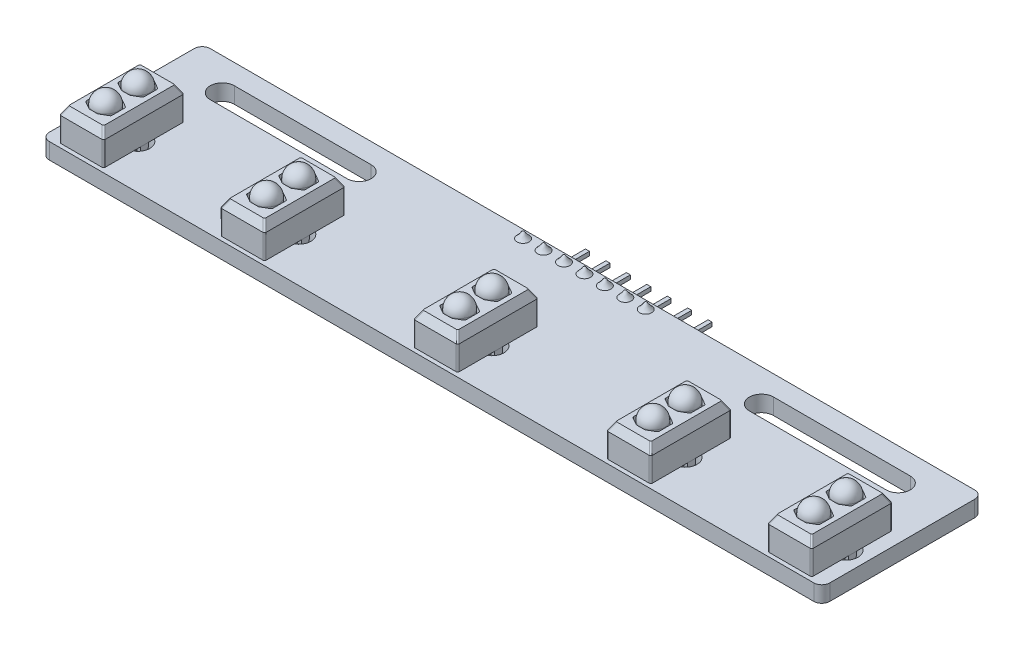
SolidWorks part; units mm, degrees
ref_plane "Front Plane" through (0, 0, 0) normal (0, 0, 1) x (1, 0, 0)
ref_plane "Top Plane" through (0, 0, 0) normal (0, 1, 0) x (1, 0, 0)
ref_plane "Right Plane" through (0, 0, 0) normal (1, 0, 0) x (0, 0, -1)
sketch "Sketch1" plane through (0, 0, 0) normal (0, 1, 0) x (1, 0, 0)
  line L0 (-42, 6) -> (-25, 6) construction
  line L1 (47.5, -10) -> (-47.5, -10)
  line L2 (48.5, -9) -> (48.5, 9)
  line L3 (47.5, 10) -> (-47.5, 10)
  line L4 (-48.5, -9) -> (-48.5, 9)
  line L5 (48.5, -10) -> (-48.5, 10) construction
  line L6 (48.5, 10) -> (-48.5, -10) construction
  line L7 (-42, 7.5) -> (-25, 7.5)
  line L8 (-42, 4.5) -> (-25, 4.5)
  line L9 (0, -55) -> (0, 55) construction
  line L10 (42, 6) -> (25, 6) construction
  line L11 (42, 7.5) -> (25, 7.5)
  line L12 (42, 4.5) -> (25, 4.5)
  arc A0 (-42, 7.5) -> (-42, 4.5) centre (-42, 6) ccw
  arc A1 (-25, 4.5) -> (-25, 7.5) centre (-25, 6) ccw
  arc A2 (42, 7.5) -> (42, 4.5) centre (42, 6) cw
  arc A3 (25, 4.5) -> (25, 7.5) centre (25, 6) cw
  circle A4 centre (-46, -4.5) radius 1.5
  circle A5 centre (-42, -4.5) radius 1.5
  circle A6 centre (-22, -4.5) radius 1.5
  circle A7 centre (-26, -4.5) radius 1.5
  circle A8 centre (-2, -4.5) radius 1.5
  circle A9 centre (2, -4.5) radius 1.5
  circle A10 centre (22, -4.5) radius 1.5
  circle A11 centre (42, -4.5) radius 1.5
  circle A12 centre (26, -4.5) radius 1.5
  circle A13 centre (46, -4.5) radius 1.5
  arc A14 (47.5, -10) -> (48.5, -9) centre (47.5, -9) ccw
  arc A15 (48.5, 9) -> (47.5, 10) centre (47.5, 9) ccw
  arc A16 (-47.5, -10) -> (-48.5, -9) centre (-47.5, -9) cw
  arc A17 (-47.5, 10) -> (-48.5, 9) centre (-47.5, 9) ccw
  point P0 (0, 0)
  point P8 (-33.5, 6)
  point P13 (-43.5, 6)
  point P14 (-23.5, 6)
  point P19 (33.5, 6)
  dimension "D7" = 3
  dimension "D13" = 1
  dimension "D1" = 97
  dimension "D2" = 20
  dimension "D3" = 20
  dimension "D4" = 3
  dimension "D5" = 2.5
  dimension "D6" = 5
  dimension "D8" = 4
  dimension "D9" = 5.5
  dimension "D10" = 2.5
  dimension "D12" = 2
  dimension "D11" = 2
extrude "Boss-Extrude1" add sketch "Sketch1" along normal blind 2
sketch "Sketch2" plane through (0, 2, 0) normal (0, 1, 0) x (1, 0, 0)
  line L0 (-47.5, -4.5) -> (-40.5, -4.5) construction
  line L1 (-46.75, -9.5) -> (-41.25, -9.5)
  line L2 (-46.75, -9.5) -> (-46.75, 0.5)
  line L3 (-46.75, 0.5) -> (-41.25, 0.5)
  line L4 (-41.25, -9.5) -> (-41.25, 0.5)
  line L5 (-46.75, -9.5) -> (-41.25, 0.5) construction
  line L6 (-46.75, 0.5) -> (-41.25, -9.5) construction
  line L7 (-26.75, -9.5) -> (-26.75, 0.5)
  line L8 (-26.75, -9.5) -> (-21.25, -9.5)
  line L9 (-21.25, -9.5) -> (-21.25, 0.5)
  line L10 (-26.75, 0.5) -> (-21.25, 0.5)
  line L11 (-2.75, -9.5) -> (-2.75, 0.5)
  line L12 (-2.75, 0.5) -> (2.75, 0.5)
  line L13 (2.75, -9.5) -> (2.75, 0.5)
  line L14 (-2.75, -9.5) -> (2.75, -9.5)
  line L15 (0, -1.1) -> (0, 1.1) construction
  line L16 (46.75, 0.5) -> (41.25, 0.5)
  line L17 (41.25, -9.5) -> (41.25, 0.5)
  line L18 (46.75, -9.5) -> (41.25, -9.5)
  line L19 (46.75, -9.5) -> (46.75, 0.5)
  line L20 (26.75, -9.5) -> (21.25, -9.5)
  line L21 (21.25, -9.5) -> (21.25, 0.5)
  line L22 (26.75, 0.5) -> (21.25, 0.5)
  line L23 (26.75, -9.5) -> (26.75, 0.5)
  circle A0 centre (-42, -4.5) radius 1.5 construction
  circle A1 centre (-46, -4.5) radius 1.5 construction
  point P0 (-44, -4.5)
  dimension "D1" = 10
  dimension "D2" = 5.5
  dimension "D3" = 2
  dimension "D4" = 2
  dimension "D5" = 2
extrude "Boss-Extrude2" add sketch "Sketch2" along normal blind 4
chamfer "Chamfer2" distance 1 angle 30 20 edges at (44, 6, 9.5) (41.25, 6, 4.5) (44, 6, -0.5) (46.75, 6, 4.5) (24, 6, 9.5) (21.25, 6, 4.5) (24, 6, -0.5) (26.75, 6, 4.5) (0, 6, 9.5) (-2.75, 6, 4.5) (0, 6, -0.5) (2.75, 6, 4.5) (-21.25, 6, 4.5) (-24, 6, 9.5) (-26.75, 6, 4.5) (-24, 6, -0.5) (-44, 6, 9.5) (-46.75, 6, 4.5) (-44, 6, -0.5) (-41.25, 6, 4.5) first distance on face at (44, 4, 9.5) first distance on face at (41.25, 3.3333, 4.5) first distance on face at (44, 4, -0.5) first distance on face at (46.75, 3.3333, 4.5) first distance on face at (24, 4, 9.5) first distance on face at (21.25, 3.3333, 4.5) first distance on face at (24, 4, -0.5) first distance on face at (26.75, 3.3333, 4.5) first distance on face at (0, 4, 9.5) first distance on face at (-2.75, 3.3333, 4.5) first distance on face at (0, 4, -0.5) first distance on face at (2.75, 3.3333, 4.5) first distance on face at (-21.25, 3.3333, 4.5) first distance on face at (-24, 4, 9.5) first distance on face at (-26.75, 3.3333, 4.5) first distance on face at (-24, 4, -0.5) first distance on face at (-44, 4, 9.5) first distance on face at (-46.75, 3.3333, 4.5) first distance on face at (-44, 4, -0.5) first distance on face at (-41.25, 3.3333, 4.5)
fillet "Fillet1" radius 0.2 40 edges at (41.25, 3.5, -0.5) (41.5387, 5.5, -0.2113) (46.75, 3.5, -0.5) (46.4613, 5.5, -0.2113) (41.25, 3.5, 9.5) (41.5387, 5.5, 9.2113) (46.75, 3.5, 9.5) (46.4613, 5.5, 9.2113) (26.75, 3.5, 9.5) (26.4613, 5.5, 9.2113) (21.25, 3.5, 9.5) (21.5387, 5.5, 9.2113) (21.25, 3.5, -0.5) (21.5387, 5.5, -0.2113) (26.4613, 5.5, -0.2113) (26.75, 3.5, -0.5) (2.75, 3.5, -0.5) (-2.75, 3.5, -0.5) (2.75, 3.5, 9.5) (-2.75, 3.5, 9.5) (-2.4613, 5.5, 9.2113) (2.4613, 5.5, 9.2113) (2.4613, 5.5, -0.2113) (-2.4613, 5.5, -0.2113) (-21.5387, 5.5, -0.2113) (-26.4613, 5.5, -0.2113) (-21.5387, 5.5, 9.2113) (-26.4613, 5.5, 9.2113) (-26.75, 3.5, 9.5) (-21.25, 3.5, 9.5) (-26.75, 3.5, -0.5) (-21.25, 3.5, -0.5) (-41.25, 3.5, -0.5) (-41.5387, 5.5, -0.2113) (-46.4613, 5.5, -0.2113) (-46.75, 3.5, -0.5) (-41.5387, 5.5, 9.2113) (-41.25, 3.5, 9.5) (-46.4613, 5.5, 9.2113) (-46.75, 3.5, 9.5)
sketch "Sketch3" plane through (0, 6, 0) normal (0, 1, 0) x (1, 0, 0)
  line L0 (-46.1726, -0.2506) -> (-46.1726, -8.7494) construction
  line L1 (-44.4849, -0.9777) -> (-43.5204, -0.9777)
  line L2 (-45.5889, -1.6996) -> (-45.5889, -3.3004)
  line L3 (-45.4889, -3.4736) -> (-44.5849, -3.9955)
  line L4 (-43.4204, -3.9955) -> (-42.5164, -3.4736)
  line L5 (-42.4164, -3.3004) -> (-42.4164, -1.6996)
  line L6 (-42.5164, -1.5264) -> (-43.4204, -1.0045)
  line L7 (-44.5849, -1.0045) -> (-45.4889, -1.5264)
  line L8 (-44.0026, -2.5) -> (-42.7184, -2.5) construction
  line L9 (-44.4849, -4.0223) -> (-43.5204, -4.0223)
  line L10 (-46.1726, -4.5) -> (-42.0545, -4.5) construction
  line L11 (-44.5849, -7.9955) -> (-45.4889, -7.4736)
  line L12 (-44.4849, -8.0223) -> (-43.5204, -8.0223)
  line L13 (-42.5164, -7.4736) -> (-43.4204, -7.9955)
  line L14 (-42.4164, -5.6996) -> (-42.4164, -7.3004)
  line L15 (-43.4204, -5.0045) -> (-42.5164, -5.5264)
  line L16 (-44.4849, -4.9777) -> (-43.5204, -4.9777)
  line L17 (-45.4889, -5.5264) -> (-44.5849, -5.0045)
  line L18 (-45.5889, -7.3004) -> (-45.5889, -5.6996)
  line L19 (-25.5889, -1.6996) -> (-25.5889, -3.3004)
  line L20 (-25.4889, -3.4736) -> (-24.5849, -3.9955)
  line L21 (-24.4849, -4.0223) -> (-23.5204, -4.0223)
  line L22 (-23.4204, -3.9955) -> (-22.5164, -3.4736)
  line L23 (-22.4164, -3.3004) -> (-22.4164, -1.6996)
  line L24 (-22.5164, -1.5264) -> (-23.4204, -1.0045)
  line L25 (-24.4849, -0.9777) -> (-23.5204, -0.9777)
  line L26 (-24.5849, -1.0045) -> (-25.4889, -1.5264)
  line L27 (-24.5849, -7.9955) -> (-25.4889, -7.4736)
  line L28 (-25.5889, -7.3004) -> (-25.5889, -5.6996)
  line L29 (-25.4889, -5.5264) -> (-24.5849, -5.0045)
  line L30 (-24.4849, -4.9777) -> (-23.5204, -4.9777)
  line L31 (-23.4204, -5.0045) -> (-22.5164, -5.5264)
  line L32 (-22.4164, -5.6996) -> (-22.4164, -7.3004)
  line L33 (-22.5164, -7.4736) -> (-23.4204, -7.9955)
  line L34 (-24.4849, -8.0223) -> (-23.5204, -8.0223)
  line L35 (-1.5889, -1.6996) -> (-1.5889, -3.3004)
  line L36 (-1.4889, -3.4736) -> (-0.5849, -3.9955)
  line L37 (-0.4849, -4.0223) -> (0.4796, -4.0223)
  line L38 (0.5796, -3.9955) -> (1.4836, -3.4736)
  line L39 (1.5836, -3.3004) -> (1.5836, -1.6996)
  line L40 (1.4836, -1.5264) -> (0.5796, -1.0045)
  line L41 (-0.4849, -0.9777) -> (0.4796, -0.9777)
  line L42 (-0.5849, -1.0045) -> (-1.4889, -1.5264)
  line L43 (-0.5849, -7.9955) -> (-1.4889, -7.4736)
  line L44 (-1.5889, -7.3004) -> (-1.5889, -5.6996)
  line L45 (-1.4889, -5.5264) -> (-0.5849, -5.0045)
  line L46 (-0.4849, -4.9777) -> (0.4796, -4.9777)
  line L47 (0.5796, -5.0045) -> (1.4836, -5.5264)
  line L48 (1.5836, -5.6996) -> (1.5836, -7.3004)
  line L49 (1.4836, -7.4736) -> (0.5796, -7.9955)
  line L50 (-0.4849, -8.0223) -> (0.4796, -8.0223)
  line L51 (0, -3.3) -> (0, 3.3) construction
  line L52 (24.4849, -8.0223) -> (23.5204, -8.0223)
  line L53 (22.5164, -7.4736) -> (23.4204, -7.9955)
  line L54 (22.4164, -5.6996) -> (22.4164, -7.3004)
  line L55 (23.4204, -5.0045) -> (22.5164, -5.5264)
  line L56 (24.4849, -4.9777) -> (23.5204, -4.9777)
  line L57 (25.4889, -5.5264) -> (24.5849, -5.0045)
  line L58 (25.5889, -7.3004) -> (25.5889, -5.6996)
  line L59 (24.5849, -7.9955) -> (25.4889, -7.4736)
  line L60 (24.5849, -1.0045) -> (25.4889, -1.5264)
  line L61 (24.4849, -0.9777) -> (23.5204, -0.9777)
  line L62 (22.5164, -1.5264) -> (23.4204, -1.0045)
  line L63 (22.4164, -3.3004) -> (22.4164, -1.6996)
  line L64 (23.4204, -3.9955) -> (22.5164, -3.4736)
  line L65 (24.4849, -4.0223) -> (23.5204, -4.0223)
  line L66 (25.4889, -3.4736) -> (24.5849, -3.9955)
  line L67 (25.5889, -1.6996) -> (25.5889, -3.3004)
  line L68 (44.4849, -8.0223) -> (43.5204, -8.0223)
  line L69 (42.5164, -7.4736) -> (43.4204, -7.9955)
  line L70 (42.4164, -5.6996) -> (42.4164, -7.3004)
  line L71 (43.4204, -5.0045) -> (42.5164, -5.5264)
  line L72 (44.4849, -4.9777) -> (43.5204, -4.9777)
  line L73 (45.4889, -5.5264) -> (44.5849, -5.0045)
  line L74 (45.5889, -7.3004) -> (45.5889, -5.6996)
  line L75 (44.5849, -7.9955) -> (45.4889, -7.4736)
  line L76 (44.5849, -1.0045) -> (45.4889, -1.5264)
  line L77 (44.4849, -0.9777) -> (43.5204, -0.9777)
  line L78 (42.5164, -1.5264) -> (43.4204, -1.0045)
  line L79 (42.4164, -3.3004) -> (42.4164, -1.6996)
  line L80 (43.4204, -3.9955) -> (42.5164, -3.4736)
  line L81 (44.4849, -4.0223) -> (43.5204, -4.0223)
  line L82 (45.4889, -3.4736) -> (44.5849, -3.9955)
  line L83 (45.5889, -1.6996) -> (45.5889, -3.3004)
  circle A0 centre (-44.0026, -2.5) radius 1.5
  circle A1 centre (-44.0026, -2.5) radius 1.5863 construction
  arc A2 (-44.4849, -4.0223) -> (-44.5849, -3.9955) centre (-44.4849, -3.8223) cw
  arc A3 (-43.5204, -4.0223) -> (-43.4204, -3.9955) centre (-43.5204, -3.8223) ccw
  arc A4 (-43.5204, -0.9777) -> (-43.4204, -1.0045) centre (-43.5204, -1.1777) cw
  arc A5 (-44.4849, -0.9777) -> (-44.5849, -1.0045) centre (-44.4849, -1.1777) ccw
  arc A6 (-42.4164, -1.6996) -> (-42.5164, -1.5264) centre (-42.6164, -1.6996) ccw
  arc A7 (-42.5164, -3.4736) -> (-42.4164, -3.3004) centre (-42.6164, -3.3004) ccw
  arc A8 (-45.5889, -3.3004) -> (-45.4889, -3.4736) centre (-45.3889, -3.3004) ccw
  arc A9 (-45.5889, -1.6996) -> (-45.4889, -1.5264) centre (-45.3889, -1.6996) cw
  arc A10 (-44.4849, -8.0223) -> (-44.5849, -7.9955) centre (-44.4849, -7.8223) cw
  arc A11 (-43.5204, -8.0223) -> (-43.4204, -7.9955) centre (-43.5204, -7.8223) ccw
  arc A12 (-42.4164, -7.3004) -> (-42.5164, -7.4736) centre (-42.6164, -7.3004) cw
  arc A13 (-42.5164, -5.5264) -> (-42.4164, -5.6996) centre (-42.6164, -5.6996) cw
  arc A14 (-43.5204, -4.9777) -> (-43.4204, -5.0045) centre (-43.5204, -5.1777) cw
  arc A15 (-44.4849, -4.9777) -> (-44.5849, -5.0045) centre (-44.4849, -5.1777) ccw
  arc A16 (-45.5889, -5.6996) -> (-45.4889, -5.5264) centre (-45.3889, -5.6996) cw
  arc A17 (-45.5889, -7.3004) -> (-45.4889, -7.4736) centre (-45.3889, -7.3004) ccw
  arc A18 (-25.5889, -1.6996) -> (-25.4889, -1.5264) centre (-25.3889, -1.6996) cw
  arc A19 (-25.5889, -3.3004) -> (-25.4889, -3.4736) centre (-25.3889, -3.3004) ccw
  arc A20 (-24.4849, -4.0223) -> (-24.5849, -3.9955) centre (-24.4849, -3.8223) cw
  arc A21 (-23.5204, -4.0223) -> (-23.4204, -3.9955) centre (-23.5204, -3.8223) ccw
  arc A22 (-22.5164, -3.4736) -> (-22.4164, -3.3004) centre (-22.6164, -3.3004) ccw
  arc A23 (-22.4164, -1.6996) -> (-22.5164, -1.5264) centre (-22.6164, -1.6996) ccw
  arc A24 (-23.5204, -0.9777) -> (-23.4204, -1.0045) centre (-23.5204, -1.1777) cw
  arc A25 (-24.4849, -0.9777) -> (-24.5849, -1.0045) centre (-24.4849, -1.1777) ccw
  arc A26 (-25.5889, -7.3004) -> (-25.4889, -7.4736) centre (-25.3889, -7.3004) ccw
  arc A27 (-25.5889, -5.6996) -> (-25.4889, -5.5264) centre (-25.3889, -5.6996) cw
  arc A28 (-24.4849, -4.9777) -> (-24.5849, -5.0045) centre (-24.4849, -5.1777) ccw
  arc A29 (-23.5204, -4.9777) -> (-23.4204, -5.0045) centre (-23.5204, -5.1777) cw
  arc A30 (-22.5164, -5.5264) -> (-22.4164, -5.6996) centre (-22.6164, -5.6996) cw
  arc A31 (-22.4164, -7.3004) -> (-22.5164, -7.4736) centre (-22.6164, -7.3004) cw
  arc A32 (-23.5204, -8.0223) -> (-23.4204, -7.9955) centre (-23.5204, -7.8223) ccw
  arc A33 (-24.4849, -8.0223) -> (-24.5849, -7.9955) centre (-24.4849, -7.8223) cw
  arc A34 (-1.5889, -3.3004) -> (-1.4889, -3.4736) centre (-1.3889, -3.3004) ccw
  arc A35 (-0.4849, -4.0223) -> (-0.5849, -3.9955) centre (-0.4849, -3.8223) cw
  arc A36 (0.4796, -4.0223) -> (0.5796, -3.9955) centre (0.4796, -3.8223) ccw
  arc A37 (1.4836, -3.4736) -> (1.5836, -3.3004) centre (1.3836, -3.3004) ccw
  arc A38 (1.5836, -1.6996) -> (1.4836, -1.5264) centre (1.3836, -1.6996) ccw
  arc A39 (0.4796, -0.9777) -> (0.5796, -1.0045) centre (0.4796, -1.1777) cw
  arc A40 (-0.4849, -0.9777) -> (-0.5849, -1.0045) centre (-0.4849, -1.1777) ccw
  arc A41 (-1.5889, -1.6996) -> (-1.4889, -1.5264) centre (-1.3889, -1.6996) cw
  arc A42 (-1.5889, -7.3004) -> (-1.4889, -7.4736) centre (-1.3889, -7.3004) ccw
  arc A43 (-1.5889, -5.6996) -> (-1.4889, -5.5264) centre (-1.3889, -5.6996) cw
  arc A44 (-0.4849, -4.9777) -> (-0.5849, -5.0045) centre (-0.4849, -5.1777) ccw
  arc A45 (0.4796, -4.9777) -> (0.5796, -5.0045) centre (0.4796, -5.1777) cw
  arc A46 (1.4836, -5.5264) -> (1.5836, -5.6996) centre (1.3836, -5.6996) cw
  arc A47 (1.5836, -7.3004) -> (1.4836, -7.4736) centre (1.3836, -7.3004) cw
  arc A48 (0.4796, -8.0223) -> (0.5796, -7.9955) centre (0.4796, -7.8223) ccw
  arc A49 (-0.4849, -8.0223) -> (-0.5849, -7.9955) centre (-0.4849, -7.8223) cw
  arc A50 (24.4849, -8.0223) -> (24.5849, -7.9955) centre (24.4849, -7.8223) ccw
  arc A51 (23.5204, -8.0223) -> (23.4204, -7.9955) centre (23.5204, -7.8223) cw
  arc A52 (22.4164, -7.3004) -> (22.5164, -7.4736) centre (22.6164, -7.3004) ccw
  arc A53 (22.5164, -5.5264) -> (22.4164, -5.6996) centre (22.6164, -5.6996) ccw
  arc A54 (23.5204, -4.9777) -> (23.4204, -5.0045) centre (23.5204, -5.1777) ccw
  arc A55 (24.4849, -4.9777) -> (24.5849, -5.0045) centre (24.4849, -5.1777) cw
  arc A56 (25.5889, -5.6996) -> (25.4889, -5.5264) centre (25.3889, -5.6996) ccw
  arc A57 (25.5889, -7.3004) -> (25.4889, -7.4736) centre (25.3889, -7.3004) cw
  arc A58 (25.5889, -1.6996) -> (25.4889, -1.5264) centre (25.3889, -1.6996) ccw
  arc A59 (24.4849, -0.9777) -> (24.5849, -1.0045) centre (24.4849, -1.1777) cw
  arc A60 (23.5204, -0.9777) -> (23.4204, -1.0045) centre (23.5204, -1.1777) ccw
  arc A61 (22.4164, -1.6996) -> (22.5164, -1.5264) centre (22.6164, -1.6996) cw
  arc A62 (22.5164, -3.4736) -> (22.4164, -3.3004) centre (22.6164, -3.3004) cw
  arc A63 (23.5204, -4.0223) -> (23.4204, -3.9955) centre (23.5204, -3.8223) cw
  arc A64 (24.4849, -4.0223) -> (24.5849, -3.9955) centre (24.4849, -3.8223) ccw
  arc A65 (25.5889, -3.3004) -> (25.4889, -3.4736) centre (25.3889, -3.3004) cw
  arc A66 (44.4849, -8.0223) -> (44.5849, -7.9955) centre (44.4849, -7.8223) ccw
  arc A67 (43.5204, -8.0223) -> (43.4204, -7.9955) centre (43.5204, -7.8223) cw
  arc A68 (42.4164, -7.3004) -> (42.5164, -7.4736) centre (42.6164, -7.3004) ccw
  arc A69 (42.5164, -5.5264) -> (42.4164, -5.6996) centre (42.6164, -5.6996) ccw
  arc A70 (43.5204, -4.9777) -> (43.4204, -5.0045) centre (43.5204, -5.1777) ccw
  arc A71 (44.4849, -4.9777) -> (44.5849, -5.0045) centre (44.4849, -5.1777) cw
  arc A72 (45.5889, -5.6996) -> (45.4889, -5.5264) centre (45.3889, -5.6996) ccw
  arc A73 (45.5889, -7.3004) -> (45.4889, -7.4736) centre (45.3889, -7.3004) cw
  arc A74 (44.4849, -0.9777) -> (44.5849, -1.0045) centre (44.4849, -1.1777) cw
  arc A75 (43.5204, -0.9777) -> (43.4204, -1.0045) centre (43.5204, -1.1777) ccw
  arc A76 (42.4164, -1.6996) -> (42.5164, -1.5264) centre (42.6164, -1.6996) cw
  arc A77 (42.5164, -3.4736) -> (42.4164, -3.3004) centre (42.6164, -3.3004) cw
  arc A78 (43.5204, -4.0223) -> (43.4204, -3.9955) centre (43.5204, -3.8223) cw
  arc A79 (44.4849, -4.0223) -> (44.5849, -3.9955) centre (44.4849, -3.8223) ccw
  arc A80 (45.5889, -3.3004) -> (45.4889, -3.4736) centre (45.3889, -3.3004) cw
  arc A81 (45.5889, -1.6996) -> (45.4889, -1.5264) centre (45.3889, -1.6996) ccw
  circle A82 centre (-44.0026, -6.5) radius 1.5
  circle A83 centre (-24.0026, -2.5) radius 1.5
  circle A84 centre (-24.0026, -6.5) radius 1.5
  circle A85 centre (-0.0026, -6.5) radius 1.5
  circle A86 centre (-0.0026, -2.5) radius 1.5
  circle A87 centre (44.0026, -6.5) radius 1.5
  circle A88 centre (44.0026, -2.5) radius 1.5
  circle A89 centre (24.0026, -6.5) radius 1.5
  circle A90 centre (24.0026, -2.5) radius 1.5
  point P2 (-46.1726, -4.5)
  point P17 (-44.5384, -4.0223)
  point P20 (-43.4668, -4.0223)
  point P23 (-43.4668, -0.9777)
  point P26 (-44.5384, -0.9777)
  dimension "D1" = 3
  dimension "D3" = 0.2
  dimension "D2" = 2
  dimension "D4" = 2
  dimension "D5" = 2
  dimension "D6" = 2
  dimension "D7" = 2
extrude "Cut-Extrude1" cut sketch "Sketch3" against normal blind 1.5
sketch "Sketch5" plane through (0, 6, 0) normal (0, 1, 0) x (1, 0, 0)
  line L0 (-43.5204, -0.9777) -> (-44.4849, -0.9777) construction
  line L1 (-44.0026, -0.9777) -> (-44.0026, -8.0223) construction
  line L2 (-44.4849, -8.0223) -> (-43.5204, -8.0223) construction
  line L3 (-42.4164, -2.5) -> (-44.0026, -2.5) construction
  line L4 (-42.4164, -3.3004) -> (-42.4164, -1.6996) construction
  line L5 (-44.0026, -1) -> (-44.0026, -4)
  line L6 (-46.75, -4.5) -> (-41.9193, -4.5) construction
  line L7 (-46.75, -9.3) -> (-46.75, 0.3) construction
  line L8 (-44.0026, -8) -> (-44.0026, -5)
  arc A0 (-44.0026, -4) -> (-44.0026, -1) centre (-44.0026, -2.5) ccw
  arc A1 (-44.0026, -5) -> (-44.0026, -8) centre (-44.0026, -6.5) cw
  dimension "D1" = 3
revolve "Revolve4" add sketch "Sketch5" angle 180 about L5
pattern_linear "LPattern2" count 2 spacing 20 along (1, 0, 0) of "Revolve4"
pattern_linear "LPattern1" count 2 spacing 44 along (1, 0, 0) of "Revolve4"
mirror "Mirror1" about plane through (0, 0, 0) normal (1, 0, 0) of "LPattern2", "Revolve4"
sketch "Sketch7" plane through (0, 0, 0) normal (0, -1, 0) x (1, 0, 0)
  line L0 (47.5, -10) -> (-47.5, -10) construction
  line L1 (-0.25, -9.25) -> (0.25, -9.25)
  line L2 (-0.25, -9.25) -> (-0.25, -8.75)
  line L3 (-0.25, -8.75) -> (0.25, -8.75)
  line L4 (0.25, -9.25) -> (0.25, -8.75)
  line L5 (-0.25, -9.25) -> (0.25, -8.75) construction
  line L6 (-0.25, -8.75) -> (0.25, -9.25) construction
  point P0 (0, -9)
  dimension "D1" = 0.5
  dimension "D2" = 0.5
  dimension "D3" = 1
sketch "Sketch8" plane through (0, 0, 0) normal (1, 0, 0) x (0, 0, -1)
  line L0 (9, 0) -> (9, -2.5)
  line L1 (9.25, 0) -> (8.75, 0) construction
  line L2 (10, -3.5) -> (17, -3.5)
  arc A0 (9, -2.5) -> (10, -3.5) centre (10, -2.5) ccw
  point P7 (9, -3.5)
  dimension "D3" = 1
  dimension "D1" = 3.5
  dimension "D2" = 8
sketch "Sketch9" plane through (0, 2, 0) normal (0, -1, 0) x (1, 0, 0)
  line L0 (-46.75, 3.201) -> (-46.75, 5.799) construction
  line L1 (-46.75, 4.9284) -> (-46.25, 4.9284)
  line L2 (-46.75, 4.9284) -> (-46.75, 3.9284)
  line L3 (-46.75, 3.9284) -> (-46.25, 3.9284)
  line L4 (-46.25, 4.9284) -> (-46.25, 3.9284)
  line L5 (-41.25, 5.799) -> (-41.25, 3.201) construction
  line L6 (-41.25, 4.9159) -> (-41.75, 4.9159)
  line L7 (-41.25, 4.9159) -> (-41.25, 3.9159)
  line L8 (-41.25, 3.9159) -> (-41.75, 3.9159)
  line L9 (-41.75, 4.9159) -> (-41.75, 3.9159)
  line L10 (-44.5, 4.5) -> (-43.5, 4.5) construction
  line L11 (-41.75, 4.4159) -> (-41.25, 4.4159) construction
  line L12 (-26.75, 4.9284) -> (-26.75, 3.9284)
  line L13 (-26.75, 4.9284) -> (-26.25, 4.9284)
  line L14 (-26.25, 4.9284) -> (-26.25, 3.9284)
  line L15 (-26.75, 3.9284) -> (-26.25, 3.9284)
  line L16 (-21.25, 4.9159) -> (-21.25, 3.9159)
  line L17 (-21.25, 4.9159) -> (-21.75, 4.9159)
  line L18 (-21.75, 4.9159) -> (-21.75, 3.9159)
  line L19 (-21.25, 3.9159) -> (-21.75, 3.9159)
  line L20 (-2.75, 4.9284) -> (-2.75, 3.9284)
  line L21 (-2.75, 3.9284) -> (-2.25, 3.9284)
  line L22 (-2.25, 4.9284) -> (-2.25, 3.9284)
  line L23 (-2.75, 4.9284) -> (-2.25, 4.9284)
  line L24 (2.75, 4.9159) -> (2.75, 3.9159)
  line L25 (2.75, 3.9159) -> (2.25, 3.9159)
  line L26 (2.25, 4.9159) -> (2.25, 3.9159)
  line L27 (2.75, 4.9159) -> (2.25, 4.9159)
  line L28 (0, -4.125) -> (0, 4.125) construction
  line L29 (21.25, 4.9159) -> (21.75, 4.9159)
  line L30 (21.75, 4.9159) -> (21.75, 3.9159)
  line L31 (21.25, 3.9159) -> (21.75, 3.9159)
  line L32 (21.25, 4.9159) -> (21.25, 3.9159)
  line L33 (26.75, 4.9284) -> (26.25, 4.9284)
  line L34 (26.25, 4.9284) -> (26.25, 3.9284)
  line L35 (26.75, 3.9284) -> (26.25, 3.9284)
  line L36 (26.75, 4.9284) -> (26.75, 3.9284)
  line L37 (41.25, 3.9159) -> (41.75, 3.9159)
  line L38 (41.75, 4.9159) -> (41.75, 3.9159)
  line L39 (41.25, 4.9159) -> (41.75, 4.9159)
  line L40 (41.25, 4.9159) -> (41.25, 3.9159)
  line L41 (46.75, 3.9284) -> (46.25, 3.9284)
  line L42 (46.25, 4.9284) -> (46.25, 3.9284)
  line L43 (46.75, 4.9284) -> (46.25, 4.9284)
  line L44 (46.75, 4.9284) -> (46.75, 3.9284)
  arc A0 (-46.75, 3.201) -> (-46.75, 5.799) centre (-46, 4.5) ccw construction
  arc A1 (-41.25, 5.799) -> (-41.25, 3.201) centre (-42, 4.5) ccw construction
  dimension "D1" = 0.5
  dimension "D2" = 1
  dimension "D3" = 1
  dimension "D4" = 0.5
  dimension "D5" = 2
  dimension "D6" = 2
extrude "Boss-Extrude4" add sketch "Sketch9" along normal blind 2 draft 2
sweep "Sweep1" add profiles "Sketch7" path "Sketch8"
pattern_linear "LPattern3" count 4 spacing 2.54 along (1, 0, 0) count 4 spacing 2.54 along (-1, 0, 0) of "Sweep1"
sketch "Sketch6" plane through (0, 0, 0) normal (0, -1, 0) x (1, 0, 0)
  line L0 (0, 0) -> (0, -8.1) construction
  line L1 (47.5, -10) -> (-47.5, -10) construction
  line L6 (1, -9.9) -> (-1, -9.9)
  line L7 (1, -9.9) -> (1, -9.8)
  line L8 (1, -7.9) -> (-1, -7.9)
  line L9 (-1, -9.9) -> (-1, -9.8)
  line L10 (3.64, -9.7) -> (3.98, -9.7)
  line L12 (3.54, -9.9) -> (3.54, -9.8)
  line L13 (3.54, -9.9) -> (1.54, -9.9)
  line L14 (1.54, -9.9) -> (1.54, -9.8)
  line L15 (3.54, -7.9) -> (1.54, -7.9)
  line L16 (6.08, -9.9) -> (6.08, -9.8)
  line L17 (6.08, -9.9) -> (4.08, -9.9)
  line L18 (4.08, -9.9) -> (4.08, -9.8)
  line L19 (6.08, -7.9) -> (4.08, -7.9)
  line L20 (8.62, -9.8) -> (8.62, -8)
  line L21 (8.52, -9.9) -> (6.62, -9.9)
  line L22 (6.62, -9.9) -> (6.62, -9.8)
  line L23 (8.52, -7.9) -> (6.62, -7.9)
  line L24 (-1.54, -9.9) -> (-1.54, -9.8)
  line L25 (-1.54, -9.9) -> (-3.54, -9.9)
  line L26 (-3.54, -9.9) -> (-3.54, -9.8)
  line L27 (-1.54, -7.9) -> (-3.54, -7.9)
  line L28 (-4.08, -9.9) -> (-4.08, -9.8)
  line L29 (-4.08, -9.9) -> (-6.08, -9.9)
  line L30 (-6.08, -9.9) -> (-6.08, -9.8)
  line L31 (-4.08, -7.9) -> (-6.08, -7.9)
  line L32 (-6.62, -9.9) -> (-6.62, -9.8)
  line L33 (-6.62, -9.9) -> (-8.62, -9.9)
  line L34 (-8.62, -9.9) -> (-8.62, -7.9)
  line L35 (-6.62, -7.9) -> (-8.62, -7.9)
  line L36 (-6.52, -8.1) -> (-6.18, -8.1)
  line L37 (-6.52, -9.7) -> (-6.18, -9.7)
  line L38 (-6.62, -8) -> (-6.62, -7.9)
  line L39 (-6.08, -8) -> (-6.08, -7.9)
  line L40 (-3.98, -8.1) -> (-3.64, -8.1)
  line L41 (-4.08, -8) -> (-4.08, -7.9)
  line L42 (-3.54, -8) -> (-3.54, -7.9)
  line L43 (-1.44, -8.1) -> (-1.1, -8.1)
  line L44 (-1.54, -8) -> (-1.54, -7.9)
  line L45 (-1, -8) -> (-1, -7.9)
  line L46 (-0.8, -8.1) -> (-1, -7.9) construction
  line L47 (1.1, -8.1) -> (1.44, -8.1)
  line L48 (0, -8.9) -> (0, -9.7) construction
  line L49 (-0.8, -9.7) -> (-1, -9.9) construction
  line L50 (1, -8) -> (1, -7.9)
  line L51 (1.54, -8) -> (1.54, -7.9)
  line L52 (3.64, -8.1) -> (3.98, -8.1)
  line L53 (3.54, -8) -> (3.54, -7.9)
  line L54 (4.08, -8) -> (4.08, -7.9)
  line L55 (6.18, -8.1) -> (6.52, -8.1)
  line L56 (6.08, -8) -> (6.08, -7.9)
  line L57 (6.62, -8) -> (6.62, -7.9)
  line L58 (-3.98, -9.7) -> (-3.64, -9.7)
  line L59 (-1.44, -9.7) -> (-1.1, -9.7)
  line L60 (1.1, -9.7) -> (1.44, -9.7)
  line L61 (0, -9.9) -> (0, -15.4294) construction
  line L62 (6.18, -9.7) -> (6.52, -9.7)
  arc A0 (1.44, -9.7) -> (1.54, -9.8) centre (1.44, -9.8) cw
  arc A1 (1.1, -9.7) -> (1, -9.8) centre (1.1, -9.8) ccw
  arc A2 (-1, -9.8) -> (-1.1, -9.7) centre (-1.1, -9.8) ccw
  arc A3 (-1.54, -9.8) -> (-1.44, -9.7) centre (-1.44, -9.8) cw
  arc A4 (-3.54, -9.8) -> (-3.64, -9.7) centre (-3.64, -9.8) ccw
  arc A5 (-4.08, -9.8) -> (-3.98, -9.7) centre (-3.98, -9.8) cw
  arc A6 (-6.08, -9.8) -> (-6.18, -9.7) centre (-6.18, -9.8) ccw
  arc A7 (-6.62, -9.8) -> (-6.52, -9.7) centre (-6.52, -9.8) cw
  arc A8 (4.08, -9.8) -> (3.98, -9.7) centre (3.98, -9.8) ccw
  arc A9 (3.54, -9.8) -> (3.64, -9.7) centre (3.64, -9.8) cw
  arc A10 (6.08, -9.8) -> (6.18, -9.7) centre (6.18, -9.8) cw
  arc A11 (6.62, -9.8) -> (6.52, -9.7) centre (6.52, -9.8) ccw
  arc A12 (8.62, -9.8) -> (8.52, -9.9) centre (8.52, -9.8) cw
  arc A13 (8.62, -8) -> (8.52, -7.9) centre (8.52, -8) ccw
  arc A14 (6.62, -8) -> (6.52, -8.1) centre (6.52, -8) cw
  arc A15 (6.18, -8.1) -> (6.08, -8) centre (6.18, -8) cw
  arc A16 (4.08, -8) -> (3.98, -8.1) centre (3.98, -8) cw
  arc A17 (3.64, -8.1) -> (3.54, -8) centre (3.64, -8) cw
  arc A18 (1.54, -8) -> (1.44, -8.1) centre (1.44, -8) cw
  arc A19 (1, -8) -> (1.1, -8.1) centre (1.1, -8) ccw
  arc A20 (-1.1, -8.1) -> (-1, -8) centre (-1.1, -8) ccw
  arc A21 (-1.44, -8.1) -> (-1.54, -8) centre (-1.44, -8) cw
  arc A22 (-3.54, -8) -> (-3.64, -8.1) centre (-3.64, -8) cw
  arc A23 (-3.98, -8.1) -> (-4.08, -8) centre (-3.98, -8) cw
  arc A24 (-6.08, -8) -> (-6.18, -8.1) centre (-6.18, -8) cw
  arc A25 (-6.52, -8.1) -> (-6.62, -8) centre (-6.52, -8) cw
  point P3 (0, -8.9)
  point P66 (1.54, -9.7)
  point P69 (1, -9.7)
  point P74 (-1.54, -9.7)
  point P77 (-3.54, -9.7)
  point P80 (-4.08, -9.7)
  point P87 (4.08, -9.7)
  point P90 (3.54, -9.7)
  point P93 (6.08, -9.7)
  point P96 (6.62, -9.7)
  point P105 (6.08, -8.1)
  point P110 (3.54, -8.1)
  point P119 (-1.54, -8.1)
  point P124 (-4.08, -8.1)
  point P129 (-6.62, -8.1)
  dimension "D8" = 0.1
  dimension "D1" = 2
  dimension "D2" = 2
  dimension "D3" = 0.1
  dimension "D4" = 4
  dimension "D5" = 4
  dimension "D6" = 0.2
  dimension "D7" = 0.2
extrude "Boss-Extrude3" add sketch "Sketch6" along normal blind 2
sketch "Sketch12" plane through (0, 0, 0) normal (1, 0, 0) x (0, 0, -1)
  line L0 (9, -2) -> (9, 2.7376) construction
  line L1 (9.25, -2) -> (8.75, -2) construction
  line L2 (9, 2) -> (-9, 2) construction
  line L3 (9, 2.792) -> (9, 1.8755)
  line L4 (9, 1.8755) -> (8.0044, 1.8755)
  spline S0 degree 3 poles (9, 2.792) (8.8682, 2.7856) (8.7666, 2.5801) (8.5001, 2.2181) (8.2595, 1.9496) (8.0044, 1.8755) knots 0 0 0 0 0.259505 0.44091 1 1 1 1
revolve "Revolve5" add sketch "Sketch12" angle 360 about L3
pattern_linear "LPattern6" count 4 spacing 2.54 along (-1, 0, 0) count 4 spacing 2.54 along (1, 0, 0) of "Revolve5"
ref_plane "Plane1" through (0, 7.5, 0) normal (0, 1, 0) x (1, 0, 0)
